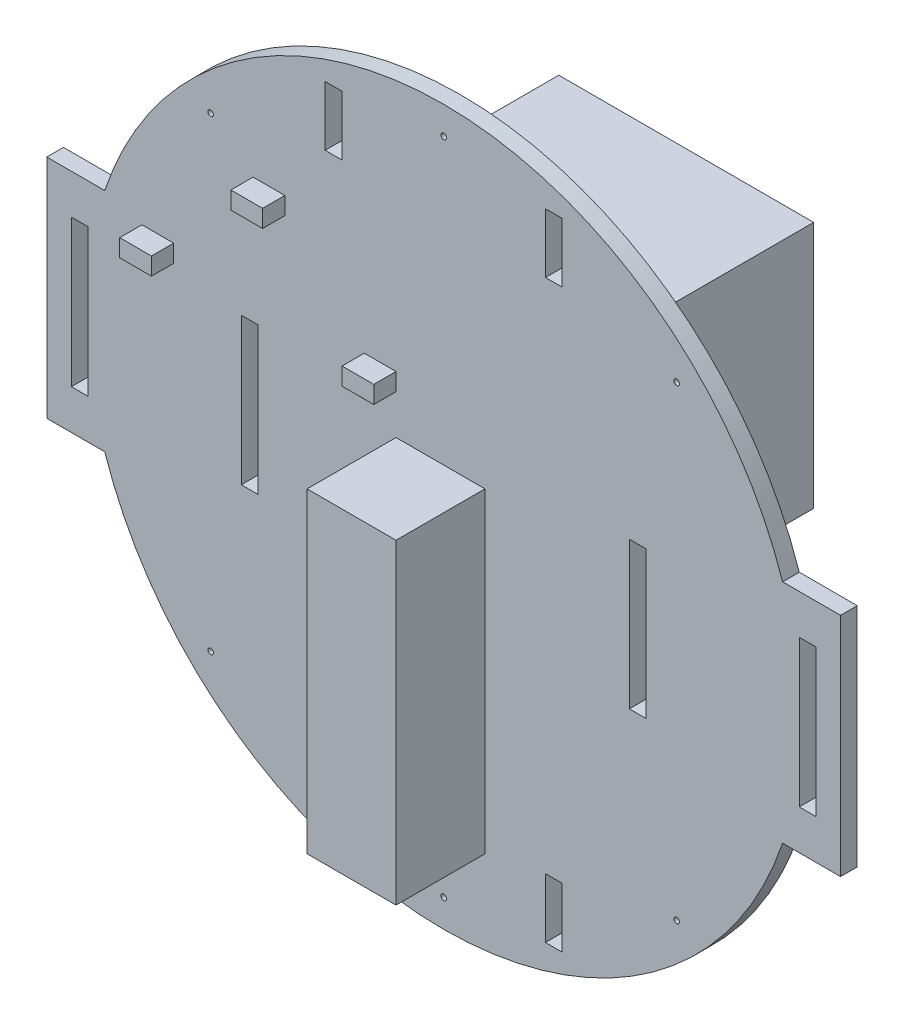
SolidWorks part; units mm, degrees
ref_plane "Front Plane" through (0, 0, 0) normal (0, 0, 1) x (1, 0, 0)
ref_plane "Top Plane" through (0, 0, 0) normal (0, 1, 0) x (1, 0, 0)
ref_plane "Right Plane" through (0, 0, 0) normal (1, 0, 0) x (0, 0, -1)
sketch "Sketch1" plane through (0, 0, 0) normal (0, 0, 1) x (1, 0, 0)
  line L0 (0, 0) -> (0, 114.3) construction
  line L1 (126.9598, -36.195) -> (108.4178, -36.195)
  line L2 (-126.9598, 36.195) -> (-108.4178, 36.195)
  line L3 (-126.9598, 36.195) -> (-126.9598, -36.195)
  line L4 (-126.9598, -36.195) -> (-108.4178, -36.195)
  line L5 (126.9598, 36.195) -> (126.9598, -36.195)
  line L6 (126.9598, 36.195) -> (108.4178, 36.195)
  line L7 (-126.9598, 23.495) -> (-113.7518, 23.495) construction
  line L8 (-108.4178, 23.495) -> (-108.4178, 36.195) construction
  line L10 (-113.7518, 23.495) -> (-113.7518, -23.495) construction
  line L11 (-113.7518, 23.495) -> (-119.0858, 23.495)
  line L12 (-113.7518, 23.495) -> (-113.7518, -23.495)
  line L13 (-108.4178, -23.495) -> (-108.4178, -36.195) construction
  line L14 (113.7518, -23.495) -> (108.4178, -23.495) construction
  line L15 (113.7518, 23.495) -> (108.4178, 23.495) construction
  line L16 (113.7518, 23.495) -> (113.7518, -23.495) construction
  line L17 (-113.7518, -23.495) -> (-119.0858, -23.495)
  line L18 (-108.4178, 23.495) -> (-64.7298, 23.495) construction
  line L19 (64.7298, 23.495) -> (64.7298, -23.495)
  line L20 (-64.7298, 23.495) -> (-59.3958, 23.495)
  line L21 (-64.7298, 23.495) -> (-64.7298, -23.495)
  line L22 (-64.7298, -23.495) -> (-59.3958, -23.495)
  line L23 (-59.3958, 23.495) -> (-59.3958, -23.495)
  line L24 (59.3958, 23.495) -> (59.3958, -23.495)
  line L25 (64.7298, -23.495) -> (59.3958, -23.495)
  line L26 (64.7298, 23.495) -> (59.3958, 23.495)
  line L27 (108.4178, 36.195) -> (108.4178, -36.195) construction
  line L28 (113.7518, 23.495) -> (119.0858, 23.495)
  line L29 (113.7518, 23.495) -> (113.7518, -23.495)
  line L30 (113.7518, -23.495) -> (119.0858, -23.495)
  line L31 (119.0858, 23.495) -> (119.0858, -23.495)
  line L32 (-119.0858, 23.495) -> (-119.0858, -23.495)
  arc A0 (-108.4178, -36.195) -> (108.4178, -36.195) centre (0, 0) ccw
  arc A1 (108.4178, 36.195) -> (-108.4178, 36.195) centre (0, 0) ccw
  dimension "D1" = 228.6
  dimension "D2" = 72.39
  dimension "D3" = 13.208
  dimension "D4" = 5.334
  dimension "D5" = 46.99
  dimension "D6" = 12.7
  dimension "D7" = 43.688
  dimension "D8" = 5.334
  dimension "D9" = 5.334
  dimension "D10" = 5.334
  dimension "D11" = 5.334
extrude "Base Platform" add sketch "Sketch1" along normal blind 5.334
sketch "Sketch3" plane through (0, 0, 5.334) normal (0, 0, 1) x (1, 0, 0)
  line L4 (-25.4, 114.3) -> (-30.48, 114.3) construction
  line L6 (-30.48, 110.1611) -> (-30.48, 63.6186) construction
  line L7 (-30.48, 63.6186) -> (-50.8, 63.6186) construction
  line L8 (-60.96, 63.6186) -> (-81.28, 63.6186) construction
  line L9 (-50.8, 63.6186) -> (-60.96, 63.6186)
  line L10 (-50.8, 63.6186) -> (-50.8, 58.0306)
  line L11 (-50.8, 58.0306) -> (-60.96, 58.0306)
  line L12 (-60.96, 63.6186) -> (-60.96, 58.0306)
  line L13 (-81.28, 63.6186) -> (-81.28, 0) construction
  line L14 (-81.28, 59.0976) -> (-86.36, 59.0976) construction
  line L15 (-86.36, 63.6186) -> (-86.36, 0) construction
  line L16 (-60.96, 58.0306) -> (-60.96, 32.6306) construction
  line L17 (-60.96, 32.6306) -> (-86.36, 32.6306) construction
  line L18 (-60.96, 32.6306) -> (-25.4, 32.6306) construction
  line L19 (-86.36, 32.6306) -> (-96.52, 32.6306)
  line L20 (-86.36, 32.6306) -> (-86.36, 27.0426)
  line L21 (-86.36, 27.0426) -> (-96.52, 27.0426)
  line L22 (-96.52, 32.6306) -> (-96.52, 27.0426)
  line L23 (-15.24, 27.0426) -> (-15.24, 14.3426) construction
  line L24 (-25.4, 32.6306) -> (-15.24, 32.6306)
  line L25 (-25.4, 32.6306) -> (-25.4, 27.0426)
  line L26 (-25.4, 27.0426) -> (-15.24, 27.0426)
  line L27 (-15.24, 32.6306) -> (-15.24, 27.0426)
  circle A0 centre (0, 0) radius 114.3 construction
  dimension "D1" = 20.32
  dimension "D2" = 10.16
  dimension "D3" = 5.588
  dimension "D4" = 20.32
  dimension "D5" = 63.6186
  dimension "D6" = 5.08
  dimension "D7" = 25.4
  dimension "D8" = 5.588
  dimension "D9" = 10.16
  dimension "D10" = 10.16
  dimension "D11" = 12.7
extrude "Track Wire Sensors" add sketch "Sketch3" along normal blind 7.112
sketch "Sketch4" plane through (0, 0, 5.334) normal (0, 0, 1) x (1, 0, 0)
  line L0 (-15.24, 27.0426) -> (-15.24, 14.3426) construction
  line L2 (-15.24, 14.3426) -> (13.208, 14.3426)
  line L3 (-15.24, 14.3426) -> (-15.24, -86.7494)
  line L4 (-15.24, -86.7494) -> (13.208, -86.7494)
  line L5 (13.208, 14.3426) -> (13.208, -86.7494)
  dimension "D1" = 12.7
  dimension "D2" = 101.092
  dimension "D3" = 28.448
extrude "Battery" add sketch "Sketch4" along normal blind 28.448
sketch "Sketch5" plane through (0, 0, 0) normal (0, 0, -1) x (-1, 0, 0)
  line L0 (0, 0) -> (0, -105.41) construction
  circle A1 centre (0, 105.41) radius 0.889
  circle A4 centre (0, -105.41) radius 0.889
  circle A5 centre (-74.5361, 74.5361) radius 0.889
  circle A6 centre (74.5361, 74.5361) radius 0.889
  circle A7 centre (74.5361, -74.5361) radius 0.889
  circle A8 centre (-74.5361, -74.5361) radius 0.889
  dimension "D1" = 1.778
  dimension "D3" = 1.778
  dimension "D4" = 1.778
  dimension "D5" = 1.778
  dimension "D6" = 1.778
  dimension "D7" = 1.778
extrude "Perimeter stacking cuts" cut sketch "Sketch5" against normal blind 5.334
sketch "Sketch6" plane through (0, 0, 0) normal (0, 0, -1) x (-1, 0, 0)
  line L4 (-32.5846, 82.5804) -> (-37.9186, 82.5804)
  line L5 (-32.5846, 82.5804) -> (-32.5846, 101.6304)
  line L6 (-32.5846, 101.6304) -> (-37.9186, 101.6304)
  line L7 (-37.9186, 82.5804) -> (-37.9186, 101.6304)
  line L8 (32.5846, 82.5804) -> (37.9186, 82.5804)
  line L9 (32.5846, 82.5804) -> (32.5846, 101.6304)
  line L10 (32.5846, 101.6304) -> (37.9186, 101.6304)
  line L11 (37.9186, 82.5804) -> (37.9186, 101.6304)
  line L17 (37.9186, -82.5804) -> (37.9186, -101.6304)
  line L18 (32.5846, -101.6304) -> (37.9186, -101.6304)
  line L19 (32.5846, -82.5804) -> (32.5846, -101.6304)
  line L20 (32.5846, -82.5804) -> (37.9186, -82.5804)
  line L21 (-37.9186, -82.5804) -> (-37.9186, -101.6304)
  line L22 (-32.5846, -101.6304) -> (-37.9186, -101.6304)
  line L23 (-32.5846, -82.5804) -> (-32.5846, -101.6304)
  line L24 (-32.5846, -82.5804) -> (-37.9186, -82.5804)
  dimension "D1" = 19.05
  dimension "D2" = 5.334
  dimension "D3" = 5.334
  dimension "D4" = 19.05
  dimension "D5" = 19.05
  dimension "D6" = 5.334
  dimension "D7" = 19.05
  dimension "D8" = 5.334
extrude "Skid Holes" cut sketch "Sketch6" against normal blind 5.334
sketch "Sketch7" plane through (0, 0, 0) normal (0, 0, -1) x (-1, 0, 0)
  line L1 (-57.15, 79.5393) -> (24.384, 79.5393)
  line L2 (-57.15, 79.5393) -> (-57.15, 0.2913)
  line L3 (-57.15, 0.2913) -> (24.384, 0.2913)
  line L4 (24.384, 79.5393) -> (24.384, 0.2913)
  dimension "D1" = 81.534
  dimension "D2" = 79.248
extrude "Uno32" add sketch "Sketch7" along normal blind 55.88
sketch "Sketch8" plane through (0, 0, 0) normal (0, 0, -1) x (-1, 0, 0)
  line L1 (30.1485, 33.4485) -> (71.0425, 33.4485)
  line L2 (30.1485, 33.4485) -> (30.1485, 74.3425)
  line L3 (30.1485, 74.3425) -> (71.0425, 74.3425)
  line L4 (71.0425, 33.4485) -> (71.0425, 74.3425)
  dimension "D1" = 40.894
  dimension "D2" = 40.894
extrude "Driver" add sketch "Sketch8" along normal blind 24.384
sketch "Sketch9" plane through (0, 0, -55.88) normal (0, 0, -1) x (-1, 0, 0)
  text T0 "Uno32\r\n"
sketch "Sketch10" plane through (0, 0, -24.384) normal (0, 0, -1) x (-1, 0, 0)
  text T0 "Driver"
sketch "Sketch11" plane through (0, 0, 0) normal (0, 0, -1) x (-1, 0, 0)
  line L1 (-57.15, -16.5114) -> (-11.43, -16.5114)
  line L2 (-57.15, -16.5114) -> (-57.15, -73.1534)
  line L3 (-57.15, -73.1534) -> (-11.43, -73.1534)
  line L4 (-11.43, -16.5114) -> (-11.43, -73.1534)
  dimension "D1" = 45.72
  dimension "D2" = 56.642
extrude "H-Bridge" add sketch "Sketch11" along normal blind 24.638
sketch "Sketch12" plane through (0, 0, -24.638) normal (0, 0, -1) x (-1, 0, 0)
  text T0 "H-Bridge"
extrude "Boss-Extrude8" add sketch "Sketch9" along normal blind 5.334
extrude "Boss-Extrude9" add sketch "Sketch10" along normal blind 5.334
extrude "Boss-Extrude10" add sketch "Sketch12" along normal blind 5.334
sketch "Sketch13" plane through (0, 0, 0) normal (0, 0, -1) x (-1, 0, 0)
  line L1 (24.384, -29.5068) -> (62.738, -29.5068)
  line L2 (24.384, -29.5068) -> (24.384, -60.2408)
  line L3 (24.384, -60.2408) -> (62.738, -60.2408)
  line L4 (62.738, -29.5068) -> (62.738, -60.2408)
  dimension "D1" = 30.734
  dimension "D2" = 38.354
extrude "Darligton Board" add sketch "Sketch13" along normal blind 23.368
sketch "Sketch14" plane through (0, 0, -23.368) normal (0, 0, -1) x (-1, 0, 0)
  text T0 "Darlington Board\r\n"
extrude "Boss-Extrude12" add sketch "Sketch14" along normal blind 5.334
